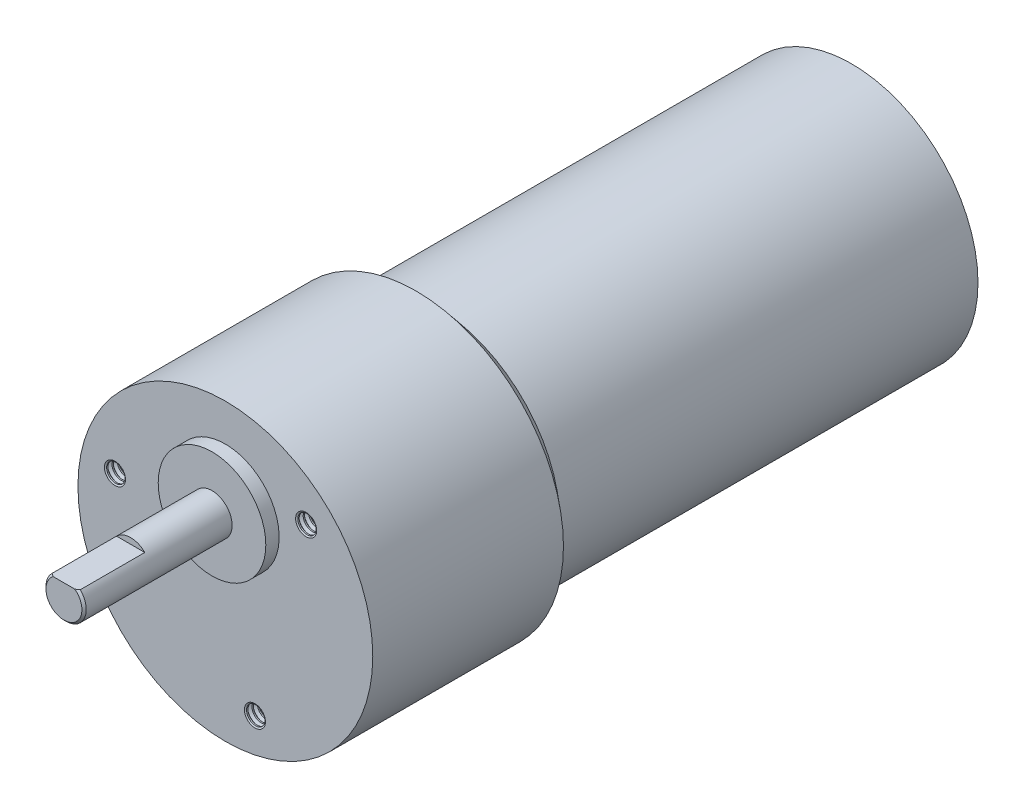
SolidWorks part; units mm, degrees
material "6061 Alloy"
ref_plane "Front" through (0, 0, 0) normal (0, 0, 1) x (1, 0, 0)
ref_plane "Top" through (0, 0, 0) normal (0, 1, 0) x (1, 0, 0)
ref_plane "Right" through (0, 0, 0) normal (1, 0, 0) x (0, 0, -1)
sketch "Sketch1" plane through (0, 0, 0) normal (0, 0, 1) x (1, 0, 0)
  circle A0 centre (0, 6.6548) radius 6.35
  dimension "D1" = 12.7
  dimension "D2" = 6.6548
extrude "Extrude1" add sketch "Sketch1" along normal blind 1.5748
sketch "Sketch2" plane through (0, 0, 0) normal (0, 0, -1) x (-1, 0, 0)
  circle A3 centre (0, 0) radius 14.9225
  dimension "D1" = 29.845
extrude "Extrude2" add sketch "Sketch2" along normal blind 73.914
sketch "Sketch3" plane through (0, 0, 0) normal (0, 0, 1) x (1, 0, 0)
  circle A0 centre (0, 6.6548) radius 2.3749
  circle A1 centre (0, 6.6548) radius 6.35 construction
  dimension "D1" = 4.7498
extrude "Extrude3" add sketch "Sketch3" along normal blind 19.05
sketch "Sketch9" plane through (0, 0, 0) normal (1, 0, 0) x (0, 0, -1)
  line L0 (51.187, 0) -> (68.6952, 0) construction
  line L1 (73.914, 0) -> (73.914, 6.35)
  line L2 (73.914, 6.35) -> (75.4888, 6.35)
  line L3 (75.4888, 6.35) -> (75.4888, 1.9812)
  line L4 (75.4888, 1.9812) -> (76.7588, 1.9812)
  line L5 (76.7588, 1.9812) -> (76.7588, 0)
  line L6 (76.7588, 0) -> (73.914, 0)
  line L7 (73.914, -14.9225) -> (73.914, 14.9225) construction
  dimension "D1" = 1.5748
  dimension "D2" = 1.27
  dimension "D3" = 3.9624
  dimension "D4" = 12.7
revolve "Revolve1" add sketch "Sketch9" angle 360 about L0
sketch "Sketch10" plane through (0, 0, 0) normal (1, 0, 0) x (0, 0, -1)
  line L0 (73.914, -14.9225) -> (73.914, 14.9225) construction
  line L1 (63.246, 22.098) -> (66.04, 22.098)
  line L2 (63.246, 22.098) -> (63.246, 0)
  line L3 (63.246, 0) -> (66.04, 0)
  line L4 (66.04, 22.098) -> (66.04, 0)
  line L5 (73.914, 0) -> (0, 0) construction
  circle A0 centre (64.643, 20.193) radius 0.5969
  point P4 (64.643, 22.098)
  dimension "D4" = 1.1938
  dimension "D5" = 1.905
  dimension "D1" = 9.271
  dimension "D2" = 2.794
  dimension "D3" = 22.098
extrude "Extrude5" [suppressed] add sketch "Sketch10" along normal mid plane 6.096
sketch "Sketch11" [suppressed] plane through (0, 0, -63.246) normal (0, 0, 1) x (1, 0, 0)
  line L0 (-2.6416, 22.098) -> (-2.6416, 14.6868)
  line L1 (-2.6416, 22.098) -> (2.6416, 22.098)
  line L2 (2.6416, 22.098) -> (2.6416, 14.6868)
  line L3 (3.048, 22.098) -> (-3.048, 22.098) construction
  line L4 (3.048, 22.098) -> (3.048, 14.6079) construction
  circle A0 centre (0, 0) radius 14.9225 construction
  arc A1 (2.6416, 14.6868) -> (-2.6416, 14.6868) centre (0, 0) ccw
  dimension "D1" = 0.4064
extrude "Cut-Extrude2" [suppressed] cut sketch "Sketch11" against normal through all
sketch "Sketch12" plane through (0, 0, 0) normal (1, 0, 0) x (0, 0, -1)
  line L0 (59.9884, 14.9225) -> (62.738, 16.51)
  line L1 (62.738, 16.51) -> (66.548, 16.51)
  line L2 (66.548, 16.51) -> (66.548, 14.9225)
  line L3 (66.548, 14.9225) -> (59.9884, 14.9225)
  line L5 (63.246, 22.098) -> (66.04, 22.098) construction
  line L8 (71.361, 0) -> (26.4089, 0) construction
  line L9 (73.914, 0) -> (0, 0) construction
  line L10 (66.04, 22.098) -> (66.04, 0) construction
  line L11 (63.246, 22.098) -> (63.246, 0) construction
  line L12 (63.246, 22.098) -> (66.04, 22.098) construction
  line L13 (66.04, 22.098) -> (66.04, 0) construction
  line L14 (63.246, 22.098) -> (63.246, 0) construction
  line L15 (73.914, 14.9225) -> (0, 14.9225) construction
  circle A0 centre (64.643, 20.193) radius 0.5969 construction
  circle A1 centre (64.643, 20.193) radius 0.5969 construction
  dimension "D1" = 16.51
  dimension "D2" = 0.508
  dimension "D3" = 0.508
  dimension "D4" = 30
revolve "Revolve2" [suppressed] add sketch "Sketch12" angle 90 mid plane about L8
sketch "Sketch13" plane through (0, 0, 0) normal (1, 0, 0) x (0, 0, -1)
  line L0 (0, 14.9225) -> (0, 17.399)
  line L1 (0, 17.399) -> (22.5092, 17.399)
  line L2 (22.5092, 17.399) -> (24.5872, 14.9225)
  line L3 (24.5872, 14.9225) -> (0, 14.9225)
  line L5 (-4.8199, 0) -> (14.8134, 0) construction
  line L6 (73.914, 0) -> (0, 0) construction
  line L7 (0, -14.9225) -> (0, 14.9225) construction
  dimension "D1" = 34.798
  dimension "D2" = 24.5872
  dimension "D3" = 50
revolve "Revolve3" add sketch "Sketch13" angle 360 about L5
ref_plane "Plane1" through (0, 0, 0) normal (0.9659, 0.2588, 0) x (0, 0, -1)
sketch "Sketch7" plane through (0, 0, 0) normal (-0.9659, -0.2588, 0) x (0, 0, -1)
  line L0 (-15.8213, 0) -> (8.2348, 0) construction
  line L1 (-0.2187, 13.4874) -> (5.9824, 13.4874) construction
  line L2 (-0.381, 13.4874) -> (5.334, 13.4874)
  line L3 (5.334, 13.4874) -> (5.334, 14.5661)
  line L4 (5.334, 14.5661) -> (5.1752, 14.5661)
  line L5 (5.1752, 14.5661) -> (4.9768, 14.9098)
  line L6 (4.9768, 14.9098) -> (4.8974, 14.9098)
  line L7 (4.8974, 14.9098) -> (4.699, 14.5661)
  line L8 (4.699, 14.5661) -> (5.1752, 14.5661) construction
  line L9 (4.9371, 14.5661) -> (4.9371, 14.9098) construction
  line L10 (-0.1826, 14.9098) -> (-0.381, 14.5661)
  line L11 (4.2624, 14.9098) -> (4.064, 14.5661)
  line L12 (4.3418, 14.9098) -> (4.2624, 14.9098)
  line L13 (4.5402, 14.5661) -> (4.3418, 14.9098)
  line L14 (4.699, 14.5661) -> (4.5402, 14.5661)
  line L15 (3.6274, 14.9098) -> (3.429, 14.5661)
  line L16 (3.7068, 14.9098) -> (3.6274, 14.9098)
  line L17 (3.9052, 14.5661) -> (3.7068, 14.9098)
  line L18 (4.064, 14.5661) -> (3.9052, 14.5661)
  line L19 (2.9924, 14.9098) -> (2.794, 14.5661)
  line L20 (3.0718, 14.9098) -> (2.9924, 14.9098)
  line L21 (3.2702, 14.5661) -> (3.0718, 14.9098)
  line L22 (3.429, 14.5661) -> (3.2702, 14.5661)
  line L23 (2.3574, 14.9098) -> (2.159, 14.5661)
  line L24 (2.4368, 14.9098) -> (2.3574, 14.9098)
  line L25 (2.6352, 14.5661) -> (2.4368, 14.9098)
  line L26 (2.794, 14.5661) -> (2.6352, 14.5661)
  line L27 (1.7224, 14.9098) -> (1.524, 14.5661)
  line L28 (1.8018, 14.9098) -> (1.7224, 14.9098)
  line L29 (2.0002, 14.5661) -> (1.8018, 14.9098)
  line L30 (2.159, 14.5661) -> (2.0002, 14.5661)
  line L31 (1.0874, 14.9098) -> (0.889, 14.5661)
  line L32 (1.1668, 14.9098) -> (1.0874, 14.9098)
  line L33 (1.3652, 14.5661) -> (1.1668, 14.9098)
  line L34 (1.524, 14.5661) -> (1.3652, 14.5661)
  line L35 (0.4524, 14.9098) -> (0.254, 14.5661)
  line L36 (0.5318, 14.9098) -> (0.4524, 14.9098)
  line L37 (0.7302, 14.5661) -> (0.5318, 14.9098)
  line L38 (0.889, 14.5661) -> (0.7302, 14.5661)
  line L40 (0, 14.9225) -> (0, -14.9225) construction
  line L41 (-0.1032, 14.9098) -> (-0.1826, 14.9098)
  line L42 (0.0952, 14.5661) -> (-0.1032, 14.9098)
  line L43 (0.254, 14.5661) -> (0.0952, 14.5661)
  line L44 (-0.381, 14.5661) -> (-0.381, 13.4874)
  dimension "D1" = 5.334
  dimension "D2" = 2.8448
  dimension "D3" = 0.635
  dimension "D4" = 60
  dimension "D5" = 0.1588
  dimension "D6" = 0.0794
  dimension "D7" = 26.9748
revolve "Cut-Revolve1" cut sketch "Sketch7" angle 360 about L1
pattern_circular "CirPattern1" count 3 over 360 about axis through (0, 0, -73.914) along (0, 0, 1) of "Cut-Revolve1"
sketch "Sketch14" plane through (0, 0, 19.05) normal (0, 0, 1) x (1, 0, 0)
  line L1 (-1.6695, 9.0297) -> (1.6695, 9.0297)
  line L2 (-1.6695, 9.0297) -> (-1.6695, 8.3439)
  line L3 (-1.6695, 8.3439) -> (1.6695, 8.3439)
  line L4 (1.6695, 9.0297) -> (1.6695, 8.3439)
  circle A0 centre (0, 6.6548) radius 2.3749 construction
  dimension "D1" = 4.064
extrude "Cut-Extrude3" cut sketch "Sketch14" against normal blind 7.874
chamfer "Chamfer1" distance 0.254 angle 45 2 edges at (0, 4.2799, 19.05) (1.9812, 0, -76.7588)
